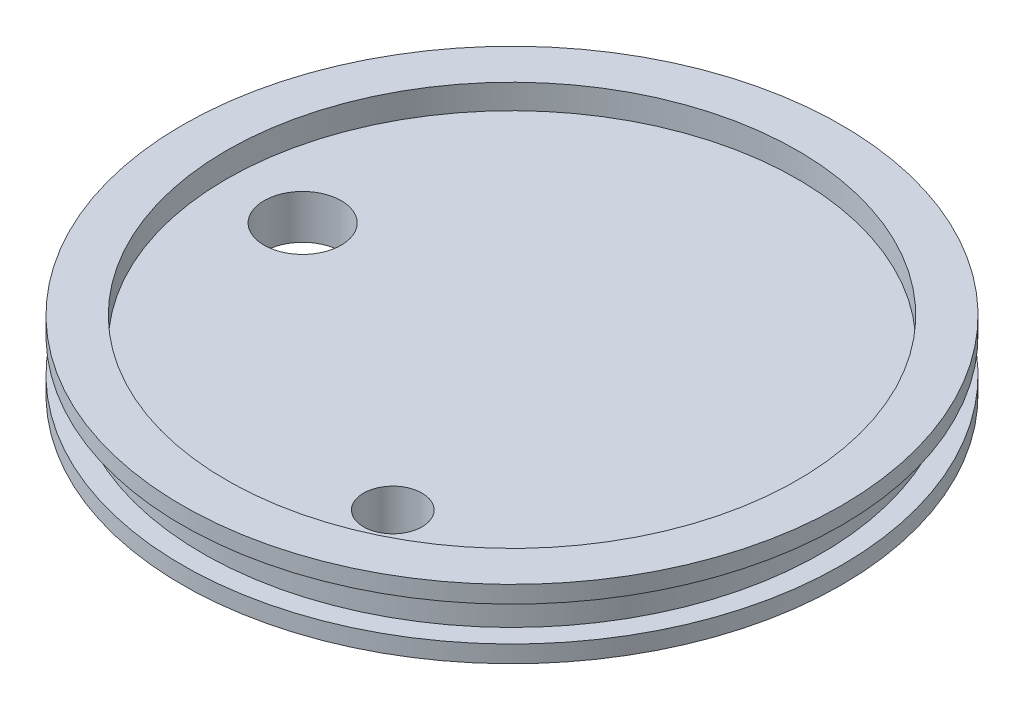
SolidWorks part; units mm, degrees
material "6061-T6 (SS)"
ref_plane "Front Plane" through (0, 0, 0) normal (0, 0, 1) x (1, 0, 0)
ref_plane "Top Plane" through (0, 0, 0) normal (0, 1, 0) x (1, 0, 0)
ref_plane "Right Plane" through (0, 0, 0) normal (1, 0, 0) x (0, 0, -1)
sketch "Sketch1" plane through (0, 0, 0) normal (0, 0, 1) x (1, 0, 0)
  line L0 (0, 48.1922) -> (0, -25.6743) construction
  line L1 (0, 0) -> (47.498, 0)
  line L2 (47.498, 0) -> (47.498, 2.4638)
  line L3 (47.498, 2.4638) -> (44.577, 2.4638)
  line L4 (44.577, 2.4638) -> (44.577, 7.4422)
  line L5 (44.577, 7.4422) -> (47.498, 7.4422)
  line L6 (47.498, 7.4422) -> (47.498, 9.906)
  line L7 (47.498, 9.906) -> (41.148, 9.906)
  line L8 (41.148, 9.906) -> (41.148, 6.35)
  line L9 (41.148, 6.35) -> (0, 6.35)
  line L10 (0, 6.35) -> (0, 0)
  dimension "D1" = 94.996
  dimension "D2" = 4.9784
  dimension "D3" = 2.921
  dimension "D4" = 9.906
  dimension "D5" = 6.35
  dimension "D6" = 6.35
revolve "Revolve1" add sketch "Sketch1" angle 360 about L0
hole_wizard "Pipe Tap Drill for 1/4 Tap1" positions "Sketch2" profile "Sketch3" hole size "1/4" standard "ANSI Inch" end condition through all
sketch "Sketch2" plane through (0, 6.35, 0) normal (0, 1, 0) x (1, 0, 0)
  point P0 (0, 0)
  point P4 (-30.1752, 0)
  dimension "D1" = 30.1752
sketch "Sketch3" plane through (0, 6.35, 0) normal (1, 0, 0) x (0, 0, 1)
  line L0 (0, 0) -> (0, 6.35)
  line L1 (0, 6.35) -> (5.5626, 6.35)
  line L2 (5.5626, 6.35) -> (5.5626, 0)
  line L5 (5.5626, 0) -> (0, 0)
  line L11 (0, -6.35) -> (0, 107.95) construction
  dimension "Thru Hole Dia." = 11.1252
  dimension "Thru Hole Depth" = 6.35
hole_wizard "Pipe Tap Drill for 1/8 Tap1" positions "Sketch4" profile "Sketch5" hole size "1/8" standard "ANSI Inch" end condition through all
sketch "Sketch4" plane through (0, 6.35, 0) normal (0, 1, 0) x (1, 0, 0)
  line L0 (0, 0) -> (12.1502, -29.3332)
  line L1 (0, 0) -> (0, -37.3592)
  point P16 (12.1502, -29.3332)
  dimension "D1" = 31.75
  dimension "D2" = 22.5
sketch "Sketch5" plane through (12.1502, 6.35, 29.3332) normal (1, 0, 0) x (0, 0, 1)
  line L0 (0, 0) -> (0, 6.35)
  line L1 (0, 6.35) -> (4.2164, 6.35)
  line L2 (4.2164, 6.35) -> (4.2164, 0)
  line L5 (4.2164, 0) -> (0, 0)
  line L11 (0, -6.35) -> (0, 107.95) construction
  dimension "Thru Hole Dia." = 8.4328
  dimension "Thru Hole Depth" = 6.35
sketch "Sketch6" plane through (0, 6.35, 0) normal (0, 1, 0) x (1, 0, 0)
  circle A0 centre (0, 0) radius 6.35
  dimension "D1" = 12.7
extrude "Boss-Extrude1" add sketch "Sketch6" against normal blind 6.35
